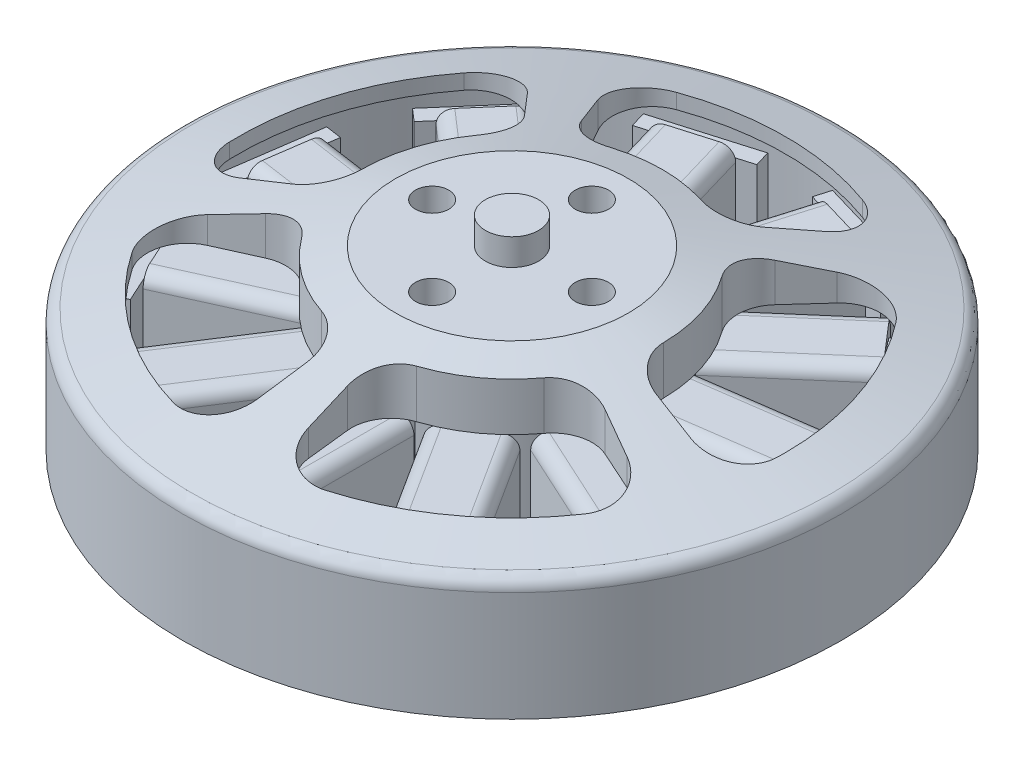
SolidWorks part; units mm, degrees
note: '?' marks a value the reader was unsure of.
material "Acero aleado"
ref_plane "Alzado" through (0, 0, 0) normal (0, 0, 1) x (1, 0, 0)
ref_plane "Planta" through (0, 0, 0) normal (0, 1, 0) x (1, 0, 0)
ref_plane "Vista lateral" through (0, 0, 0) normal (1, 0, 0) x (0, 0, -1)
sketch "Croquis1" plane through (0, 0, 0) normal (0, 1, 0) x (1, 0, 0)
  circle A0 centre (0, 0) radius 24.75
  dimension "D1" = 49.5
extrude "Saliente-Extruir1" add sketch "Croquis1" along normal blind 9
sketch "Croquis2" plane through (0, 0, 0) normal (0, 0, 1) x (1, 0, 0)
  line L0 (-24.75, 9) -> (-8.75, 13.3)
  line L1 (-8.75, 13.3) -> (0, 13.3)
  line L2 (0, 13.3) -> (0, 9)
  line L3 (24.75, 9) -> (-24.75, 9) construction
  line L4 (0, 9) -> (-24.75, 9)
  dimension "D1" = 8.75
  dimension "D2" = 4.3
revolve "Revolución1" add sketch "Croquis2" angle 360 about L2
sketch "Croquis4" plane through (0, 0, 0) normal (0, -1, 0) x (1, 0, 0)
  circle A0 centre (0, 0) radius 22.8389
extrude "Cortar-Extruir1" cut sketch "Croquis4" against normal blind 9
sketch "Croquis5" plane through (0, 13.3, 0) normal (0, 1, 0) x (1, 0, 0)
  line L0 (-8.5704, 15.019) -> (-6.9301, 12.1446)
  line L1 (6.9301, 12.1446) -> (8.5704, 15.019)
  line L2 (0, 0) -> (0, 27.6667) construction
  line L3 (11.6356, 12.7921) -> (9.4086, 10.3438)
  line L4 (13.6917, -2.8381) -> (16.9324, -3.5098)
  line L5 (15.7616, -7.1131) -> (12.745, -5.7517)
  line L6 (1.5318, -13.8986) -> (1.8944, -17.1882)
  line L7 (-1.8944, -17.1882) -> (-1.5318, -13.8986)
  line L8 (-12.745, -5.7517) -> (-15.7616, -7.1131)
  line L9 (-16.9324, -3.5098) -> (-13.6917, -2.8381)
  line L10 (-9.4086, 10.3438) -> (-11.6356, 12.7921)
  arc A0 (3.4173, 10.7719) -> (-3.4173, 10.7719) centre (0, 0) ccw
  arc A1 (6.9844, 19.3273) -> (-6.9844, 19.3273) centre (0, 0) ccw
  arc A2 (6.9301, 12.1446) -> (3.4173, 10.7719) centre (4.3245, 13.6314) cw
  arc A3 (-6.9301, 12.1446) -> (-3.4173, 10.7719) centre (-4.3245, 13.6314) ccw
  arc A4 (8.5704, 15.019) -> (6.9844, 19.3273) centre (5.9648, 16.5059) ccw
  arc A5 (-8.5704, 15.019) -> (-6.9844, 19.3273) centre (-5.9648, 16.5059) cw
  arc A6 (11.3007, 0.0786) -> (9.1887, 6.5788) centre (0, 0) ccw
  arc A7 (20.5397, -0.6701) -> (16.2231, 12.615) centre (0, 0) ccw
  arc A8 (13.6917, -2.8381) -> (11.3007, 0.0786) centre (14.3006, 0.0995) cw
  arc A9 (9.4086, 10.3438) -> (9.1887, 6.5788) centre (11.6279, 8.3252) ccw
  arc A10 (16.9324, -3.5098) -> (20.5397, -0.6701) centre (17.5413, -0.5723) ccw
  arc A11 (11.6356, 12.7921) -> (16.2231, 12.615) centre (13.8548, 10.7735) cw
  arc A12 (3.5669, -10.7233) -> (9.0962, -6.706) centre (0, 0) ccw
  arc A13 (5.7098, -19.7415) -> (17.0108, -11.5308) centre (0, 0) ccw
  arc A14 (1.5318, -13.8986) -> (3.5669, -10.7233) centre (4.5137, -13.57) cw
  arc A15 (12.745, -5.7517) -> (9.0962, -6.706) centre (11.511, -8.4862) ccw
  arc A16 (1.8944, -17.1882) -> (5.7098, -19.7415) centre (4.8763, -16.8596) ccw
  arc A17 (15.7616, -7.1131) -> (17.0108, -11.5308) centre (14.5276, -9.8475) cw
  arc A18 (-9.0962, -6.706) -> (-3.5669, -10.7233) centre (0, 0) ccw
  arc A19 (-17.0108, -11.5308) -> (-5.7098, -19.7415) centre (0, 0) ccw
  arc A20 (-12.745, -5.7517) -> (-9.0962, -6.706) centre (-11.511, -8.4862) cw
  arc A21 (-1.5318, -13.8986) -> (-3.5669, -10.7233) centre (-4.5137, -13.57) ccw
  arc A22 (-15.7616, -7.1131) -> (-17.0108, -11.5308) centre (-14.5276, -9.8475) ccw
  arc A23 (-1.8944, -17.1882) -> (-5.7098, -19.7415) centre (-4.8763, -16.8596) cw
  arc A24 (-9.1887, 6.5788) -> (-11.3007, 0.0786) centre (0, 0) ccw
  arc A25 (-16.2231, 12.615) -> (-20.5397, -0.6701) centre (0, 0) ccw
  arc A26 (-9.4086, 10.3438) -> (-9.1887, 6.5788) centre (-11.6279, 8.3252) cw
  arc A27 (-13.6917, -2.8381) -> (-11.3007, 0.0786) centre (-14.3006, 0.0995) ccw
  arc A28 (-11.6356, 12.7921) -> (-16.2231, 12.615) centre (-13.8548, 10.7735) ccw
  arc A29 (-16.9324, -3.5098) -> (-20.5397, -0.6701) centre (-17.5413, -0.5723) cw
  point P65 (0, 0)
  dimension "D1" = 3
  dimension "D2" = 5
extrude "Cortar-Extruir2" cut sketch "Croquis5" against normal through all
sketch "Croquis3" plane through (0, 13.3, 0) normal (0, 1, 0) x (1, 0, 0)
  circle A0 centre (0, 0) radius 2
  dimension "D1" = 4
extrude "Saliente-Extruir2" add sketch "Croquis3" along normal blind 8 from offset 6 offset against normal yes
sketch "Croquis6" plane through (0, 7.3, 0) normal (0, -1, 0) x (1, 0, 0)
  line L0 (-1.4178, 20.2309) -> (-1.4178, 8.6919)
  line L1 (1.4178, 20.2309) -> (1.4178, 8.6919)
  line L2 (0, 0) -> (0, 19.3794) construction
  line L3 (-1.4178, 20.2309) -> (-3.7639, 20.2309)
  line L4 (-3.7639, 20.2309) -> (-3.7639, 21.4518)
  line L5 (-3.7639, 21.4518) -> (3.7639, 21.4518)
  line L6 (3.7639, 21.4518) -> (3.7639, 20.2309)
  line L7 (3.7639, 20.2309) -> (1.4178, 20.2309)
  line L8 (9.745, 17.7858) -> (3.5065, 8.0786)
  line L9 (12.1304, 16.2528) -> (5.8919, 6.5456)
  line L10 (9.745, 17.7858) -> (7.7713, 19.0542)
  line L11 (7.7713, 19.0542) -> (8.4313, 20.0813)
  line L12 (8.4313, 20.0813) -> (14.7641, 16.0115)
  line L13 (14.7641, 16.0115) -> (14.1041, 14.9844)
  line L14 (14.1041, 14.9844) -> (12.1304, 16.2528)
  line L15 (17.8137, 9.6939) -> (7.3175, 4.9004)
  line L16 (18.9916, 7.1146) -> (8.4954, 2.3211)
  line L17 (17.8137, 9.6939) -> (16.8391, 11.828)
  line L18 (16.8391, 11.828) -> (17.9496, 12.3352)
  line L19 (17.9496, 12.3352) -> (21.0768, 5.4876)
  line L20 (21.0768, 5.4876) -> (19.9663, 4.9805)
  line L21 (19.9663, 4.9805) -> (18.9916, 7.1146)
  line L22 (20.2268, -1.4758) -> (8.8052, 0.1663)
  line L23 (19.8232, -4.2825) -> (8.4017, -2.6403)
  line L24 (20.2268, -1.4758) -> (20.5606, 0.8464)
  line L25 (20.5606, 0.8464) -> (21.7691, 0.6727)
  line L26 (21.7691, 0.6727) -> (20.6978, -6.7785)
  line L27 (20.6978, -6.7785) -> (19.4893, -6.6047)
  line L28 (19.4893, -6.6047) -> (19.8232, -4.2825)
  line L29 (16.2179, -12.177) -> (7.4974, -4.6205)
  line L30 (14.3611, -14.3199) -> (5.6405, -6.7635)
  line L31 (16.2179, -12.177) -> (17.7543, -10.4039)
  line L32 (17.7543, -10.4039) -> (18.677, -11.2034)
  line L33 (18.677, -11.2034) -> (13.7473, -16.8925)
  line L34 (13.7473, -16.8925) -> (12.8247, -16.093)
  line L35 (12.8247, -16.093) -> (14.3611, -14.3199)
  line L36 (7.06, -19.012) -> (3.8091, -7.9404)
  line L37 (4.3394, -19.8108) -> (1.0885, -8.7393)
  line L38 (7.06, -19.012) -> (9.3111, -18.351)
  line L39 (9.3111, -18.351) -> (9.6551, -19.5224)
  line L40 (9.6551, -19.5224) -> (2.4322, -21.6432)
  line L41 (2.4322, -21.6432) -> (2.0883, -20.4718)
  line L42 (2.0883, -20.4718) -> (4.3394, -19.8108)
  line L43 (-4.3394, -19.8108) -> (-1.0885, -8.7393)
  line L44 (-7.06, -19.012) -> (-3.8091, -7.9404)
  line L45 (-4.3394, -19.8108) -> (-2.0883, -20.4718)
  line L46 (-2.0883, -20.4718) -> (-2.4322, -21.6432)
  line L47 (-2.4322, -21.6432) -> (-9.6551, -19.5224)
  line L48 (-9.6551, -19.5224) -> (-9.3111, -18.351)
  line L49 (-9.3111, -18.351) -> (-7.06, -19.012)
  line L50 (-14.3611, -14.3199) -> (-5.6405, -6.7635)
  line L51 (-16.2179, -12.177) -> (-7.4974, -4.6205)
  line L52 (-14.3611, -14.3199) -> (-12.8247, -16.093)
  line L53 (-12.8247, -16.093) -> (-13.7473, -16.8925)
  line L54 (-13.7473, -16.8925) -> (-18.677, -11.2034)
  line L55 (-18.677, -11.2034) -> (-17.7543, -10.4039)
  line L56 (-17.7543, -10.4039) -> (-16.2179, -12.177)
  line L57 (-19.8232, -4.2825) -> (-8.4017, -2.6403)
  line L58 (-20.2268, -1.4758) -> (-8.8052, 0.1663)
  line L59 (-19.8232, -4.2825) -> (-19.4893, -6.6047)
  line L60 (-19.4893, -6.6047) -> (-20.6978, -6.7785)
  line L61 (-20.6978, -6.7785) -> (-21.7691, 0.6727)
  line L62 (-21.7691, 0.6727) -> (-20.5606, 0.8464)
  line L63 (-20.5606, 0.8464) -> (-20.2268, -1.4758)
  line L64 (-18.9916, 7.1146) -> (-8.4954, 2.3211)
  line L65 (-17.8137, 9.6939) -> (-7.3175, 4.9004)
  line L66 (-18.9916, 7.1146) -> (-19.9663, 4.9805)
  line L67 (-19.9663, 4.9805) -> (-21.0768, 5.4876)
  line L68 (-21.0768, 5.4876) -> (-17.9496, 12.3352)
  line L69 (-17.9496, 12.3352) -> (-16.8391, 11.828)
  line L70 (-16.8391, 11.828) -> (-17.8137, 9.6939)
  line L71 (-12.1304, 16.2528) -> (-5.8919, 6.5456)
  line L72 (-9.745, 17.7858) -> (-3.5065, 8.0786)
  line L73 (-12.1304, 16.2528) -> (-14.1041, 14.9844)
  line L74 (-14.1041, 14.9844) -> (-14.7641, 16.0115)
  line L75 (-14.7641, 16.0115) -> (-8.4313, 20.0813)
  line L76 (-8.4313, 20.0813) -> (-7.7713, 19.0542)
  line L77 (-7.7713, 19.0542) -> (-9.745, 17.7858)
  arc A0 (-5.8919, 6.5456) -> (-7.3175, 4.9004) centre (0, 0) ccw
  arc A1 (3.5065, 8.0786) -> (1.4178, 8.6919) centre (0, 0) ccw
  arc A2 (7.3175, 4.9004) -> (5.8919, 6.5456) centre (0, 0) ccw
  arc A3 (8.8052, 0.1663) -> (8.4954, 2.3211) centre (0, 0) ccw
  arc A4 (7.4974, -4.6205) -> (8.4017, -2.6403) centre (0, 0) ccw
  arc A5 (3.8091, -7.9404) -> (5.6405, -6.7635) centre (0, 0) ccw
  arc A6 (-1.0885, -8.7393) -> (1.0885, -8.7393) centre (0, 0) ccw
  arc A7 (-5.6405, -6.7635) -> (-3.8091, -7.9404) centre (0, 0) ccw
  arc A8 (-8.4017, -2.6403) -> (-7.4974, -4.6205) centre (0, 0) ccw
  arc A10 (-8.4954, 2.3211) -> (-8.8052, 0.1663) centre (0, 0) ccw
  arc A11 (-1.4178, 8.6919) -> (-3.5065, 8.0786) centre (0, 0) ccw
  point P93 (0, 0)
  dimension "D1" = 11
extrude "Saliente-Extruir3" add sketch "Croquis6" along normal blind 8
sketch "Croquis7" plane through (0, -0.7, 0) normal (0, -1, 0) x (1, 0, 0)
  circle A0 centre (0, 0) radius 7.5
  dimension "D1" = 15
extrude "Saliente-Extruir4" add sketch "Croquis7" along normal blind 5
sketch "Croquis8" plane through (0, -5.7, 0) normal (0, -1, 0) x (1, 0, 0)
  circle A0 centre (0, 0) radius 12.25
  dimension "D1" = 24.5
extrude "Saliente-Extruir5" add sketch "Croquis8" along normal blind 1.2
sketch "Croquis9" plane through (0, -6.9, 0) normal (0, -1, 0) x (1, 0, 0)
  circle A0 centre (0, 0) radius 2
  dimension "D1" = 4
extrude "Saliente-Extruir6" add sketch "Croquis9" along normal blind 16
sketch "Croquis11" plane through (0, 13.3, 0) normal (0, 1, 0) x (1, 0, 0)
  circle A0 centre (0, 0) radius 6 construction
  circle A1 centre (0, -6) radius 1.25
  circle A2 centre (6, 0) radius 1.25
  circle A3 centre (0, 6) radius 1.25
  circle A4 centre (-6, 0) radius 1.25
  dimension "D1" = 12
  dimension "D2" = 2.5
extrude "Cortar-Extruir3" cut sketch "Croquis11" against normal blind 3
sketch "Croquis12" plane through (0, -6.9, 0) normal (0, -1, 0) x (1, 0, 0)
  line L0 (0, -8) -> (0, 8) construction
  line L1 (-9.5, 0) -> (9.5, 0) construction
  circle A0 centre (0, 8) radius 1.3484
  circle A1 centre (0, -8) radius 1.3484
  circle A2 centre (-9.5, 0) radius 1.3484
  circle A3 centre (9.5, 0) radius 1.3484
  point P4 (0, 0)
  point P10 (0, 0)
  dimension "D1" = 16
  dimension "D2" = 19
extrude "Cortar-Extruir4" cut sketch "Croquis12" against normal blind 6
sketch "Croquis13" plane through (0, -5.7, 0) normal (0, 1, 0) x (1, 0, 0)
  line L0 (-6.9089, 2.7478) -> (-3.1846, 6.4721)
  line L1 (-3.1846, 6.4721) -> (-16.0348, 19.3223)
  line L2 (-16.0348, 19.3223) -> (-19.7591, 15.598)
  line L3 (-19.7591, 15.598) -> (-6.9089, 2.7478)
extrude "Saliente-Extruir8" add sketch "Croquis13" along normal blind 2 from offset 1
sketch "Croquis14" plane through (0, 15.3, 0) normal (0, 1, 0) x (1, 0, 0)
  circle A0 centre (0, 0) radius 2
  dimension "D1" = 4
extrude "Cortar-Extruir5" cut sketch "Croquis14" against normal through all
sketch "Croquis15" plane through (-21.2334, 0, -3.0529) normal (-0.9898, 0, -0.1423) x (-0.1423, 0, 0.9898)
  line L0 (-7.5, -0.7) -> (7.5, -0.7) construction
  line L1 (-1.151, 7.5583) -> (1.151, 7.5583)
  line L2 (-1.151, 7.5583) -> (-1.151, -0.7)
  line L3 (-1.151, -0.7) -> (1.151, -0.7)
  line L4 (1.151, 7.5583) -> (1.151, -0.7)
  line L5 (-1.151, 7.5583) -> (1.151, -0.7) construction
  line L6 (-1.151, -0.7) -> (1.151, 7.5583) construction
  line L7 (9.745, -0.7) -> (3.5065, -0.7) construction
  line L8 (3.7639, -0.7) -> (-3.7639, -0.7) construction
  line L9 (-2.6274, 8.2468) -> (2.6274, 8.2468)
  line L10 (-2.6274, 8.2468) -> (-2.6274, -1.3885)
  line L11 (-2.6274, -1.3885) -> (2.6274, -1.3885)
  line L12 (2.6274, 8.2468) -> (2.6274, -1.3885)
  line L13 (-2.6274, 8.2468) -> (2.6274, -1.3885) construction
  line L14 (-2.6274, -1.3885) -> (2.6274, 8.2468) construction
  point P0 (0, 3.4291)
  point P9 (0, 3.4291)
extrude "Saliente-Extruir9" add sketch "Croquis15" against normal blind 10 from offset 1.5 offset against normal yes
fillet "Redondeo1" radius 1 4 edges at (-14.4257, 8.2468, -4.7285) (-15.1735, 8.2468, 0.4728) (-14.4257, -1.3885, -4.7285) (-15.1735, -1.3885, 0.4728)
ref_axis "Eje1" through (0, 14.31, 0) along (0, -1, 0)?
pattern_circular "MatrizC1" count 11 over 360 about axis through (0, 14.31, 0) along (0, -1, 0) of "Saliente-Extruir9", "Redondeo1"
fillet "Redondeo2" radius 1 1 edges at (0, 9, 24.75)
sketch "Croquis16" plane through (0, 13.3, 0) normal (0, 1, 0) x (1, 0, 0)
  circle A0 centre (0, 0) radius 2
extrude "Saliente-Extruir10" add sketch "Croquis16" against normal blind 24 from offset 2
